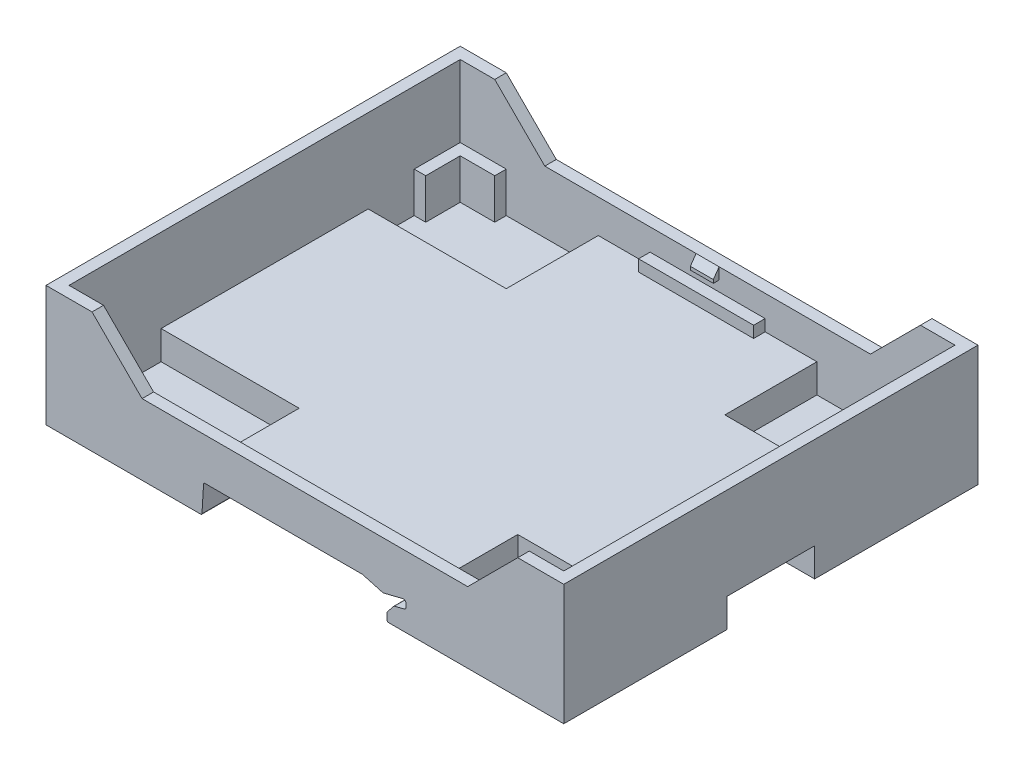
SolidWorks part; units mm, degrees
ref_plane "前视基准面" through (0, 0, 0) normal (0, 0, 1) x (1, 0, 0)
ref_plane "上视基准面" through (0, 0, 0) normal (0, 1, 0) x (1, 0, 0)
ref_plane "右视基准面" through (0, 0, 0) normal (1, 0, 0) x (0, 0, -1)
other "Configuration Table"
sketch "草图1" plane through (0, 0, 0) normal (0, 1, 0) x (1, 0, 0)
  line L1 (-45, -36) -> (45, -36)
  line L2 (-45, -36) -> (-45, 36)
  line L3 (-45, 36) -> (45, 36)
  line L4 (45, -36) -> (45, 36)
  dimension "D1" = 72
  dimension "D2" = 90
  dimension "D3" = 45
  dimension "D4" = 36
extrude "凸台-拉伸1" add sketch "草图1" along normal blind 21
sketch "草图4" plane through (0, 0, 36) normal (0, 0, 1) x (1, 0, 0)
  line L0 (14.3, 0) -> (14.3, 1.5)
  line L1 (-45, 0) -> (45, 0) construction
  line L2 (15.49, 2.9653) -> (17.6, 3.5)
  line L3 (17.6, 3.5) -> (17.6, 5)
  line L4 (17.6, 5) -> (13.5989, 4.0036)
  line L5 (13.5989, 4.0036) -> (10, 5)
  line L6 (10, 5) -> (-17.6, 5)
  line L7 (-17.6, 5) -> (-17.9, 0)
  line L8 (-17.9, 0) -> (14.3, 0)
  line L10 (14.3, 1.5) -> (15.49, 2.9653)
  dimension "D1" = 35.2
  dimension "D2" = 209.46
  dimension "D3" = 7.6
  dimension "D4" = 17.6
  dimension "D5" = 0.3
  dimension "D6" = 14.22
  dimension "D7" = 3.3
  dimension "D8" = 309.08
  dimension "D9" = 1.5
  dimension "D10" = 1.5
  dimension "D11" = 5
extrude "切除-拉伸1" cut sketch "草图4" against normal blind 72
fillet "圆角1" radius 0.5 2 edges at (17.6, 3.5, 0) (17.6, 5, 0)
fillet "圆角2" radius 0.2 5 edges at (-17.9, 0, 0) (-17.6, 5, 0) (15.49, 2.9653, 0) (14.3, 1.5, 0) (14.3, 0, 0)
sketch "草图5" plane through (-45, 0, 0) normal (-1, 0, 0) x (0, 0, 1)
  line L0 (5.6, 0) -> (5.6, 2.4)
  line L1 (-36, 0) -> (36, 0) construction
  line L2 (5.6, 2.4) -> (7.6, 2.4)
  line L3 (7.6, 2.4) -> (7.6, 5)
  line L4 (7.6, 5) -> (-7.6, 5)
  line L5 (-7.6, 5) -> (-7.6, 2.4)
  line L6 (-7.6, 2.4) -> (-5.6, 2.4)
  line L7 (-5.6, 2.4) -> (-5.6, 0)
  line L8 (-5.6, 0) -> (5.6, 0)
  dimension "D1" = 11.2
  dimension "D2" = 5.6
  dimension "D3" = 5
  dimension "D4" = 2.4
  dimension "D5" = 2.4
  dimension "D6" = 15.2
  dimension "D7" = 7.6
extrude "切除-拉伸2" cut sketch "草图5" against normal blind 28
sketch "草图6" plane through (0, 0, 0) normal (0, -1, 0) x (1, 0, 0)
  line L0 (-18.0884, 5.6) -> (-45, 5.6) construction
  line L1 (-33, 5.6) -> (-28, 5.6)
  line L2 (-33, 5.6) -> (-33, 7.6)
  line L3 (-33, 7.6) -> (-28, 7.6)
  line L4 (-28, 5.6) -> (-28, 7.6)
  line L5 (-45, 5.6) -> (-45, 36) construction
  line L6 (-17.756, 7.6) -> (-45, 7.6) construction
  dimension "D1" = 5
  dimension "D3" = 12
extrude "切除-拉伸3" cut sketch "草图6" against normal blind 2.4
ref_plane "基准面1" through (0, 0, 0) normal (0, 0, -1) x (-1, 0, 0)
mirror "镜向1" about plane through (0, 0, 0) normal (0, 0, -1) of "切除-拉伸3"
fillet "圆角3" radius 0.5 2 edges at (-31.2058, 5, -7.6) (-31.2058, 5, 7.6)
sketch "草图7" plane through (0, 5, 0) normal (0, -1, 0) x (1, 0, 0)
  line L0 (-33, 3.2) -> (-33, -3.2)
  line L1 (-33, -3.2) -> (-28, -3.2)
  line L2 (-28, -3.2) -> (-32, -1)
  line L3 (-32, -1) -> (-32, 1)
  line L4 (-32, 1) -> (-28, 3.2)
  line L5 (-28, 3.2) -> (-33, 3.2)
  line L8 (-33, 7.6) -> (-33, 5.6) construction
  line L9 (-11.55, 0) -> (11.55, 0) construction
  dimension "D1" = 5
  dimension "D2" = 1
  dimension "D3" = 6.4
  dimension "D4" = 2
  dimension "D5" = 1
  dimension "D6" = 3.2
extrude "凸台-拉伸2" add sketch "草图7" along normal blind 3.5
fillet "圆角4" radius 1 2 edges at (-32, 3.25, -1) (-32, 3.25, 1)
fillet "圆角5" radius 0.3 2 edges at (-28, 3.25, -3.2) (-28, 3.25, 3.2)
chamfer "倒角1" distance 1 angle 45 2 edges at (-33, 3.25, 3.2) (-33, 3.25, -3.2)
sketch "草图8" plane through (0, 5, 0) normal (0, -1, 0) x (1, 0, 0)
  line L0 (-11.55, 0) -> (11.55, 0) construction
  line L1 (-37.36, 2) -> (-34.46, 2)
  line L2 (-37.36, 2) -> (-37.36, -2)
  line L3 (-37.36, -2) -> (-34.46, -2)
  line L4 (-34.46, 2) -> (-34.46, -2)
  line L5 (-33, 2.2) -> (-33, -2.2) construction
  dimension "D1" = 4
  dimension "D2" = 2
  dimension "D3" = 2.9
  dimension "D4" = 1.46
extrude "凸台-拉伸3" add sketch "草图8" along normal blind 2.5
chamfer "倒角2" distance 2 angle 35 1 edges at (-34.46, 2.5, 0) first distance on face at (-35.91, 2.5, 0)
fillet "圆角6" radius 0.2 10 edges at (-35.91, 5, 2) (-34.46, 5, 0) (-37.36, 3.75, 2) (-37.36, 2.5, 0) (-37.36, 5, 0) (-35.91, 5, -2) (-37.36, 3.75, -2) (-36.91, 2.5, -2) (-35.46, 3.2002, -2) (-34.46, 4.4502, -2)
fillet "圆角7" radius 0.3 2 edges at (-36.4785, 2.5586, -1.9414) (-36.46, 2.5, 0.1)
fillet "圆角8" radius 0.2 2 edges at (-34.5186, 3.9309, -1.9414) (-34.46, 3.9004, 0.1)
sketch "草图9" plane through (45, 0, 0) normal (1, 0, 0) x (0, 0, -1)
  line L0 (-36, 0) -> (36, 0) construction
  line L1 (7.6, 0) -> (-7.6, 0)
  line L2 (7.6, 0) -> (7.6, 5)
  line L3 (7.6, 5) -> (-7.6, 5)
  line L4 (-7.6, 0) -> (-7.6, 5)
  dimension "D1" = 15.2
  dimension "D2" = 7.6
  dimension "D3" = 5
extrude "切除-拉伸4" cut sketch "草图9" against normal blind 36
sketch "草图10" plane through (0, 0, 7.6) normal (0, 0, -1) x (-1, 0, 0)
  line L0 (-14.5, 0) -> (-45, 0) construction
  line L1 (-10, 5) -> (-17.6, 5)
  line L2 (-10, 5) -> (-10, 0)
  line L3 (-10, 0) -> (-17.6, 0)
  line L4 (-17.6, 5) -> (-17.6, 0)
  line L5 (-17.6, 4.3602) -> (-17.6, 3.8891) construction
extrude "切除-拉伸5" cut sketch "草图10" against normal blind 4
mirror "镜向2" about plane through (0, 0, 0) normal (0, 0, -1) of "切除-拉伸5"
sketch "草图11" plane through (0, 0, 36) normal (0, 0, 1) x (1, 0, 0)
  line L0 (-37, 21) -> (37, 21)
  line L1 (-45, 21) -> (45, 21) construction
  line L2 (37, 21) -> (28.3, 12.3)
  line L3 (28.3, 12.3) -> (-28.3, 12.3)
  line L4 (-28.3, 12.3) -> (-37, 21)
  dimension "D1" = 56.6
  dimension "D2" = 28.3
  dimension "D3" = 8.7
  dimension "D4" = 135
  dimension "D5" = 135
extrude "切除-拉伸6" cut sketch "草图11" against normal blind 72
sketch "草图12" plane through (0, 21, 0) normal (0, 1, 0) x (1, 0, 0)
  line L0 (-37, 36) -> (-45, 36) construction
  line L1 (-43, 34) -> (43, 34)
  line L2 (-43, 34) -> (-43, -34)
  line L3 (-43, -34) -> (43, -34)
  line L4 (43, 34) -> (43, -34)
  line L5 (45, -36) -> (45, 36) construction
  line L6 (37, -36) -> (45, -36) construction
  line L7 (-45, 36) -> (-45, -36) construction
  dimension "D1" = 2
  dimension "D2" = 2
  dimension "D3" = 2
  dimension "D4" = 2
extrude "切除-拉伸7" cut sketch "草图12" against normal blind 14.5
sketch "草图13" plane through (0, 6.5, 0) normal (0, 1, 0) x (1, 0, 0)
  line L1 (43, -34) -> (19, -34)
  line L2 (43, -34) -> (43, -18)
  line L3 (43, -18) -> (19, -18)
  line L4 (19, -34) -> (19, -18)
  dimension "D1" = 16
  dimension "D2" = 24
extrude "切除-拉伸8" cut sketch "草图13" against normal blind 5
ref_plane "基准面3" through (0, 0, 0) normal (-1, 0, 0) x (0, 0, 1)
mirror "镜向3" about plane through (0, 0, 0) normal (0, 0, -1) of "切除-拉伸8"
mirror "镜向4" about plane through (0, 0, 0) normal (-1, 0, 0) of "镜向3"
sketch "草图14" plane through (0, 1.5, 0) normal (0, 1, 0) x (1, 0, 0)
  line L0 (35, -34) -> (43, -34)
  line L1 (37, -34) -> (43, -34) construction
  line L2 (43, -34) -> (43, -26)
  line L3 (43, -34) -> (43, -18) construction
  line L4 (43, -26) -> (41, -26)
  line L5 (41, -26) -> (41, -32)
  line L6 (41, -32) -> (35, -32)
  line L7 (35, -32) -> (35, -34)
  dimension "D1" = 2
  dimension "D2" = 2
  dimension "D3" = 8
  dimension "D4" = 8
extrude "凸台-拉伸4" add sketch "草图14" along normal blind 7
mirror "镜向5" about plane through (0, 0, 0) normal (0, 0, -1) of "凸台-拉伸4"
mirror "镜向6" about plane through (0, 0, 0) normal (-1, 0, 0) of "镜向5"
sketch "草图15" plane through (0, 6.5, 0) normal (0, 1, 0) x (1, 0, 0)
  line L12 (19, 34) -> (-19, 34) construction
  line L13 (-10, 34) -> (10, 34)
  line L14 (-10, 34) -> (-10, 32)
  line L15 (-10, 32) -> (10, 32)
  line L16 (10, 34) -> (10, 32)
  line L18 (0, 11.55) -> (0, -11.55) construction
  dimension "D1" = 20
  dimension "D2" = 10
  dimension "D3" = 2
extrude "凸台-拉伸5" add sketch "草图15" along normal blind 2
mirror "镜向7" about plane through (0, 0, 0) normal (0, 0, -1) of "凸台-拉伸5"
sketch "草图17" plane through (0, 0, -34) normal (0, 0, 1) x (1, 0, 0)
  line L0 (-28.3, 12.3) -> (28.3, 12.3) construction
  line L1 (-2, 12.3) -> (2, 12.3)
  line L2 (-2, 12.3) -> (-2, 10.3)
  line L3 (-2, 10.3) -> (2, 10.3)
  line L4 (2, 12.3) -> (2, 10.3)
  line L5 (10, 8.5) -> (-10, 8.5) construction
  line L6 (0, 11.55) -> (0, -11.55) construction
  dimension "D1" = 1.8
  dimension "D2" = 4
  dimension "D3" = 2
extrude "凸台-拉伸6" add sketch "草图17" along normal blind 1
chamfer "倒角3" distance 1 angle 55 1 edges at (0, 12.3, -33) first distance on face at (0, 12.3, -34.25)
mirror "镜向8" about plane through (0, 0, 0) normal (0, 0, -1) of "倒角3", "凸台-拉伸6"
sketch "草图20" plane through (0, 8.5, 0) normal (0, 1, 0) x (1, 0, 0)
  line L0 (-10, -33.8) -> (10, -33.8)
  line L1 (19, -33.8) -> (42.8, -33.8)
  line L14 (-28.3, 34) -> (-2, 34) construction
  line L16 (-42.8, 33.8) -> (-19, 33.8)
  line L17 (-42.8, 33.8) -> (-42.8, -33.8)
  line L20 (-42.8, -33.8) -> (-19, -33.8)
  line L21 (42.8, 33.8) -> (42.8, -33.8)
  line L25 (-43, 34) -> (-43, -34) construction
  line L26 (43, -18) -> (43, 18) construction
  line L63 (35, -34) -> (43, -34) construction
  line L64 (-19, 33.8) -> (-19, 28.8)
  line L65 (-19, 18) -> (-19, 34) construction
  line L66 (-19, 18) -> (-19, 34) construction
  line L67 (-19, 28.8) -> (-10, 28.8)
  line L68 (-10, 28.8) -> (-10, 33.8)
  line L69 (-10, 34) -> (-10, 32) construction
  line L70 (19, 33.8) -> (19, 28.8)
  line L71 (19, 18) -> (19, 34) construction
  line L72 (19, 28.8) -> (10, 28.8)
  line L73 (10, 28.8) -> (10, 33.8)
  line L74 (10, 32) -> (10, 34) construction
  line L75 (-10, -33.8) -> (-10, -28.8)
  line L76 (-10, -28.8) -> (-19, -28.8)
  line L77 (-19, -18) -> (-19, -34) construction
  line L78 (-19, -28.8) -> (-19, -33.8)
  line L79 (-19, -18) -> (-19, -34) construction
  line L80 (19, -33.8) -> (19, -28.8)
  line L81 (19, -18) -> (19, -34) construction
  line L82 (19, -28.8) -> (10, -28.8)
  line L83 (10, -28.8) -> (10, -33.8)
  line L84 (10, -32) -> (10, -34) construction
  line L85 (19, 33.8) -> (42.8, 33.8)
  line L86 (-10, 33.8) -> (10, 33.8)
  dimension "D1" = 0.2
  dimension "D2" = 0.2
  dimension "D3" = 0.2
  dimension "D4" = 0.2
  dimension "D5" = 5
  dimension "D6" = 5
  dimension "D7" = 5
  dimension "D8" = 5
